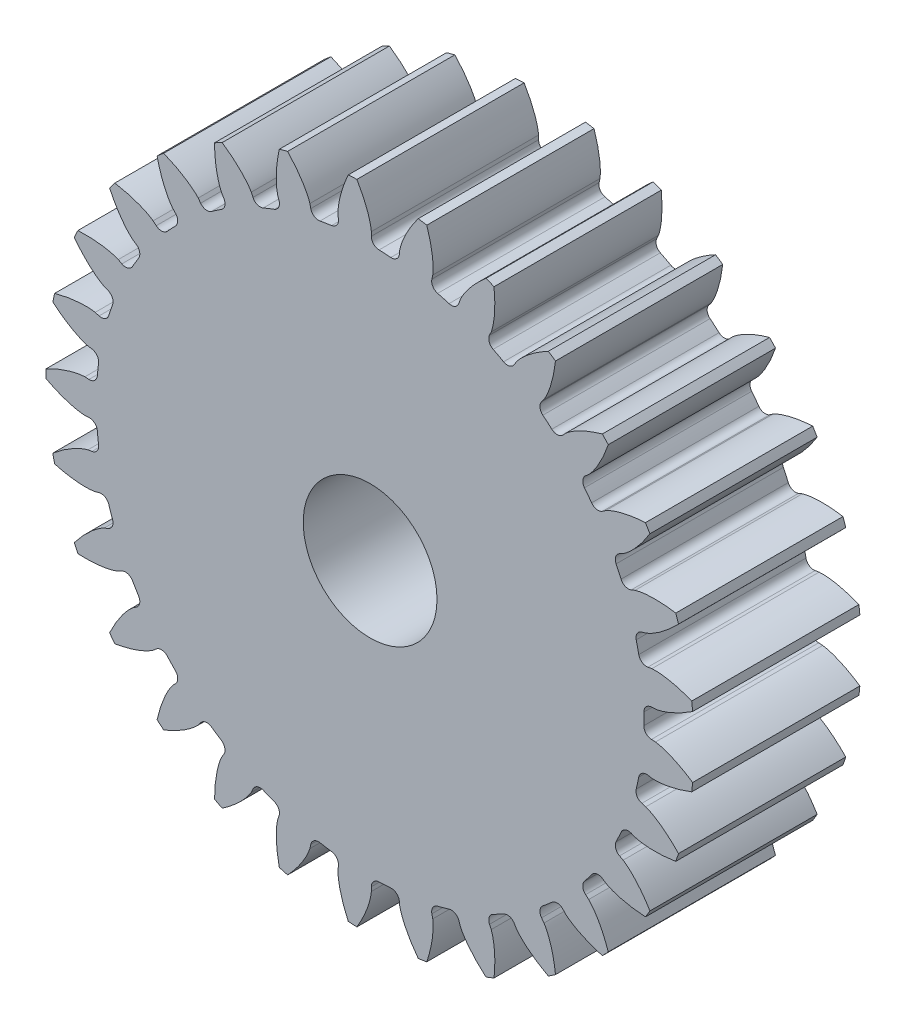
SolidWorks part; units mm, degrees
ref_plane "Front Plane" through (0, 0, 0) normal (0, 0, 1) x (1, 0, 0)
ref_plane "Top Plane" through (0, 0, 0) normal (0, 1, 0) x (1, 0, 0)
ref_plane "Right Plane" through (0, 0, 0) normal (1, 0, 0) x (0, 0, -1)
ref_axis "Gear Axis" through (0, 0, -0.5001) along (0, 0, 1)
sketch "Blank Sketch" plane through (0, 0, 0) normal (0, 0, 1) x (1, 0, 0)
  circle A0 centre (0, 0) radius 19.375
  dimension "OD" = 38.75
extrude "Blank" add sketch "Blank Sketch" along normal blind 10
sketch "Tooth Space Sketch" plane through (0, 0, 0) normal (0, 0, 1) x (1, 0, 0)
  line L0 (17.0663, 0.8503) -> (16.8224, 0.8381)
  line L1 (17.0663, -0.8503) -> (16.8224, -0.8381)
  line L2 (20.4418, 2.7425) -> (20.4418, -2.7425)
  arc A0 (16.8224, 0.8381) -> (16.3712, 0.3535) centre (16.8461, 0.3637) ccw
  arc A1 (16.3712, -0.3535) -> (16.8224, -0.8381) centre (16.8461, -0.3637) ccw
  arc A2 (16.3712, -0.3535) -> (16.3712, 0.3535) centre (0, 0) ccw
  spline S0 degree 4 poles (17.0135, 0.8446) (17.0293, 0.846) (17.0578, 0.8489) (17.0923, 0.8537) (17.1704, 0.8664) (17.2415, 0.8815) (17.3413, 0.9044) (17.4429, 0.9322) (17.5589, 0.9668) (17.6732, 1.0049) (17.7886, 1.0463) (17.9017, 1.0901) (18.029, 1.1425) (18.1822, 1.2098) (18.3618, 1.295) (18.5645, 1.3991) (18.7783, 1.5182) (18.9862, 1.6416) (19.1939, 1.7741) (19.3924, 1.907) (19.5966, 2.0534) (19.7819, 2.1909) (19.989, 2.3557) (20.1509, 2.4871) (20.3673, 2.6752) (20.4862, 2.7818) (20.6292, 2.914) (20.6918, 2.9739) (20.7288, 3.0093) knots 0 0 0 0 0 0.011935 0.024895 0.042157 0.060774 0.086082 0.114007 0.141932 0.169857 0.197782 0.225707 0.253632 0.295827 0.351677 0.407526 0.463377 0.519226 0.575076 0.630926 0.686776 0.742626 0.798476 0.854326 0.910176 0.955088 1 1 1 1 1 construction
  spline S1 degree 4 poles (17.0663, 0.8503) (17.0789, 0.8519) (17.1077, 0.8562) (17.1704, 0.8664) (17.2415, 0.8815) (17.3413, 0.9044) (17.4429, 0.9322) (17.5589, 0.9668) (17.6732, 1.0049) (17.7886, 1.0463) (17.9017, 1.0901) (18.029, 1.1425) (18.1822, 1.2098) (18.3618, 1.295) (18.5645, 1.3991) (18.7783, 1.5182) (18.9862, 1.6416) (19.1939, 1.7741) (19.3924, 1.907) (19.5966, 2.0534) (19.7819, 2.1909) (19.989, 2.3557) (20.1509, 2.4871) (20.3216, 2.6355) (20.4012, 2.706) (20.4418, 2.7425) knots 0.011935 0.011935 0.011935 0.011935 0.011935 0.024895 0.042157 0.060774 0.086082 0.114007 0.141932 0.169857 0.197782 0.225707 0.253632 0.295827 0.351677 0.407526 0.463377 0.519226 0.575076 0.630926 0.686776 0.742626 0.798476 0.854326 0.910176 0.910176 0.910176 0.910176 0.910176
  spline S2 degree 4 poles (17.0135, -0.8446) (17.0293, -0.846) (17.0578, -0.8489) (17.0923, -0.8537) (17.1704, -0.8664) (17.2415, -0.8815) (17.3413, -0.9044) (17.4429, -0.9322) (17.5589, -0.9668) (17.6732, -1.0049) (17.7886, -1.0463) (17.9017, -1.0901) (18.029, -1.1425) (18.1822, -1.2098) (18.3618, -1.295) (18.5645, -1.3991) (18.7783, -1.5182) (18.9862, -1.6416) (19.1939, -1.7741) (19.3924, -1.907) (19.5966, -2.0534) (19.7819, -2.1909) (19.989, -2.3557) (20.1509, -2.4871) (20.3673, -2.6752) (20.4862, -2.7818) (20.6292, -2.914) (20.6918, -2.9739) (20.7288, -3.0093) knots 0 0 0 0 0 0.011935 0.024895 0.042157 0.060774 0.086082 0.114007 0.141932 0.169857 0.197782 0.225707 0.253632 0.295827 0.351677 0.407526 0.463377 0.519226 0.575076 0.630926 0.686776 0.742626 0.798476 0.854326 0.910176 0.955088 1 1 1 1 1 construction
  spline S3 degree 4 poles (17.0663, -0.8503) (17.0789, -0.8519) (17.1077, -0.8562) (17.1704, -0.8664) (17.2415, -0.8815) (17.3413, -0.9044) (17.4429, -0.9322) (17.5589, -0.9668) (17.6732, -1.0049) (17.7886, -1.0463) (17.9017, -1.0901) (18.029, -1.1425) (18.1822, -1.2098) (18.3618, -1.295) (18.5645, -1.3991) (18.7783, -1.5182) (18.9862, -1.6416) (19.1939, -1.7741) (19.3924, -1.907) (19.5966, -2.0534) (19.7819, -2.1909) (19.989, -2.3557) (20.1509, -2.4871) (20.3216, -2.6355) (20.4012, -2.706) (20.4418, -2.7425) knots 0.011935 0.011935 0.011935 0.011935 0.011935 0.024895 0.042157 0.060774 0.086082 0.114007 0.141932 0.169857 0.197782 0.225707 0.253632 0.295827 0.351677 0.407526 0.463377 0.519226 0.575076 0.630926 0.686776 0.742626 0.798476 0.854326 0.910176 0.910176 0.910176 0.910176 0.910176
  dimension "Root" = 16.375
  dimension "Fillet" = 0.475
extrude "Tooth Space" cut sketch "Tooth Space Sketch" against normal through all both and the other way through all both
pattern_circular "Teeth" count 29 over 360 about axis through (0, 0, -0.5001) along (0, 0, 1) of "Tooth Space"
sketch "Bore Sketch" plane through (0, 0, 0) normal (0, 0, 1) x (1, 0, 0)
  circle A0 centre (0, 0) radius 4
  dimension "Bore" = 8
extrude "Bore" cut sketch "Bore Sketch" against normal through all both and the other way through all both
equation "\"No. of Teeth\"= 29"
equation "\"Module\"= 1.25"
equation "\"Bore Diameter\"= 8"
equation "\"Pressure Angle\"= 20"
equation "\"Outer Diameter\"= ( \"No. of Teeth\" + 2 ) * \"Module\""
equation "\"Pitch Diameter\"= \"No. of Teeth\" * \"Module\""
equation "\"Backlash\"= 0.3 * \"Module\""
equation "\"Arc Length\"= ( ( \"Module\" * pi ) / 2 + \"Backlash\" )"
equation "\"Fillet Radius\"= 0.38 * \"Module\""
equation "\"Tooth Depth\"= IIF ( \"Module\" <= 1.25 , \"Module\" * 2.4 , \"Module\" * 2.25 )"
equation "\"Face Width\"= 10"
equation "\"Root Diameter\"= \"Outer Diameter\" - 2 * \"Tooth Depth\""
equation "\"Base Diameter\"= \"Pitch Diameter\" * cos ( \"Pressure Angle\" )"
equation "\"Base Radius\"= \"Base Diameter\" / 2"
equation "\"Tooth Thickness\"= \"Module\" * pi - \"Arc Length\""
equation "\"Half Space Angle\"= ( \"Arc Length\" / \"Pitch Diameter\" ) * 180 / pi"
equation "\"Involute Fn\"= tan ( \"Pressure Angle\" ) - \"Pressure Angle\" * pi / 180"
equation "\"Flank Offset\"= \"Arc Length\" / \"Pitch Diameter\" - \"Involute Fn\""
equation "\"Tip Cap Diameter\"= \"Outer Diameter\" + 2 * \"Module\""
equation "\"Flank Start Diameter\"= IIF ( \"Base Diameter\" >= ( \"Root Diameter\" + 3 * \"Fillet Radius\" ) , \"Base Diameter\" , \"Root Diameter\" + 3 * \"Fillet Radius\" )"
equation "\"Involute t1\"= ( abs ( ( \"Flank Start Diameter\" / \"Base Diameter\" ) ^ 2 - 1 ) ) ^ 0.5"
equation "\"Involute t2\"= ( abs ( ( \"Tip Cap Diameter\" / \"Base Diameter\" ) ^ 2 - 1 ) ) ^ 0.5"
equation "\"Flank Arc Radius\"= ( \"Pitch Diameter\" / 2 ) * sin ( \"Pressure Angle\" )"
equation "\"Flank Centre Angle\"= \"Half Space Angle\" + \"Pressure Angle\""
equation "\"OD@Blank Sketch\"= \"Outer Diameter\""
equation "\"Width@Blank\"= \"Face Width\""
equation "\"Root@Tooth Space Sketch\"= \"Root Diameter\" / 2"
equation "\"Fillet@Tooth Space Sketch\"= \"Fillet Radius\""
equation "\"Count@Teeth\"= \"No. of Teeth\""
equation "\"Bore@Bore Sketch\"= \"Bore Diameter\""
